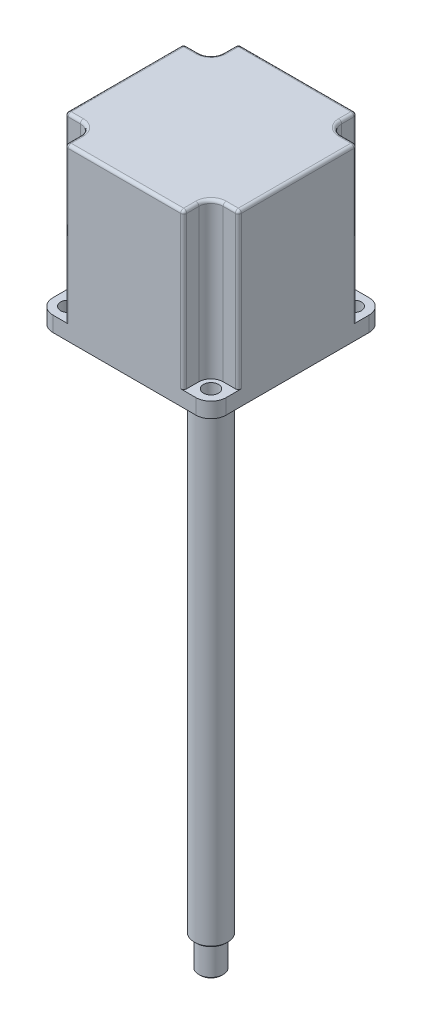
SolidWorks part; units mm, degrees
note: '?' marks a value the reader was unsure of.
material "1023 Carbon Steel Sheet (SS)"
ref_plane "Front" through (0, 0, 0) normal (0, 0, 1) x (1, 0, 0)
ref_plane "Top" through (0, 0, 0) normal (0, 1, 0) x (1, 0, 0)
ref_plane "Right" through (0, 0, 0) normal (1, 0, 0) x (0, 0, -1)
ref_axis "Axis1" through (-84.4107, 0, 0) along (1, 0, 0)?
ref_axis "Axis2" through (0, 64.3378, 0) along (0, -1, 0)?
ref_axis "Axis3" through (0, 0, -102.329) along (0, 0, 1)?
sketch "Sketch1" plane through (0, 0, 0) normal (0, 1, 0) x (1, 0, 0)
  line L1 (-28.5, -28.5) -> (28.5, -28.5)
  line L2 (-28.5, -28.5) -> (-28.5, 28.5)
  line L3 (-28.5, 28.5) -> (28.5, 28.5)
  line L4 (28.5, -28.5) -> (28.5, 28.5)
  line L5 (-28.5, -28.5) -> (28.5, 28.5) construction
  line L6 (-28.5, 28.5) -> (28.5, -28.5) construction
  point P0 (0, 0)
  dimension "D1" = 57
  dimension "D2" = 57
extrude "Extrude1" add sketch "Sketch1" along normal blind 76
hole_wizard "Ø5.0 (5) Diameter Hole1" positions "Sketch5" profile "Sketch4" hole size "Ø5.0" standard "ISO" end condition through all
sketch "Sketch5" plane through (0, 0, 0) normal (0, -1, 0) x (1, 0, 0)
  line L0 (-28.5, 28.5) -> (28.5, -28.5) construction
  line L3 (28.5, 28.5) -> (-28.5, -28.5) construction
  point P0 (-23.5, 23.5)
  point P1 (23.5, 23.5)
  point P3 (23.5, -23.5)
  point P5 (-23.5, -23.5)
  dimension "D1" = 47
  dimension "D2" = 47
sketch "Sketch4" plane through (-23.5, 0, 23.5) normal (1, 0, 0) x (0, 0, -1)
  line L0 (0, 0) -> (0, 76)
  line L1 (0, 76) -> (2.5, 76)
  line L2 (2.5, 76) -> (2.5, 0)
  line L5 (2.5, 0) -> (0, 0)
  line L11 (0, -6.35) -> (0, 107.95) construction
  dimension "Thru Hole Dia." = 5
  dimension "Thru Hole Depth" = 76
sketch "Sketch6" plane through (0, 76, 0) normal (0, 1, 0) x (1, 0, 0)
  line L0 (-19.5, 23.5) -> (-19.5, 32.5117)
  line L1 (-19.5, 32.5117) -> (-33.9089, 32.5117)
  line L2 (-33.9089, 32.5117) -> (-33.9089, 19.5)
  line L3 (-33.9089, 19.5) -> (-23.5, 19.5)
  line L4 (19.5, 23.5) -> (19.5, 36.4716)
  line L5 (19.5, 36.4716) -> (41.1684, 36.4716)
  line L6 (41.1684, 36.4716) -> (41.1684, 19.5)
  line L7 (41.1684, 19.5) -> (23.5, 19.5)
  line L8 (23.5, -19.5) -> (44.2522, -19.5)
  line L9 (44.2522, -19.5) -> (44.2522, -40.0504)
  line L10 (44.2522, -40.0504) -> (19.5, -40.0504)
  line L11 (19.5, -40.0504) -> (19.5, -23.5)
  line L12 (-23.5, -19.5) -> (-37.6708, -19.5)
  line L13 (-37.6708, -19.5) -> (-37.6708, -37.8282)
  line L14 (-37.6708, -37.8282) -> (-19.5, -37.8282)
  line L15 (-19.5, -37.8282) -> (-19.5, -23.5)
  circle A0 centre (-23.5, 23.5) radius 4
  circle A1 centre (23.5, 23.5) radius 4
  circle A2 centre (23.5, -23.5) radius 4
  circle A3 centre (-23.5, -23.5) radius 4
  circle M1 centre (-23.5, -23.5) radius 2.5
  circle M2 centre (23.5, -23.5) radius 2.5
  circle M3 centre (23.5, 23.5) radius 2.5
  circle M4 centre (-23.5, 23.5) radius 2.5
  line M5 (28.5, -28.5) -> (28.5, 28.5)
  line M6 (28.5, 28.5) -> (-28.5, 28.5)
  line M7 (-28.5, 28.5) -> (-28.5, -28.5)
  line M8 (-28.5, -28.5) -> (28.5, -28.5)
  dimension "D1" = 8
  dimension "D2" = 8
  dimension "D3" = 8
  dimension "D4" = 8
extrude "Extrude4" cut sketch "Sketch6" against normal blind 71 contours L2 L3 L0 L1 M7 M6 | A0 L0 L3 M6 M7 | A0 M4 | L7 L6 L5 L4 M6 M5 | A1 L7 L4 M5 M6 | A1 M3 | A2 M2 | A2 L11 L8 M8 M5 | L11 L10 L9 L8 M5 M8 | L14 L15 L12 L13 M8 M7 | A3 L12 L15 M7 M8 | A3 M1
fillet "Fillet1" radius 5 4 edges at (-28.5, 2.5, 28.5) (28.5, 2.5, 28.5) (28.5, 2.5, -28.5) (-28.5, 2.5, -28.5)
sketch "Sketch7" plane through (0, 76, 0) normal (0, 1, 0) x (1, 0, 0)
  circle A0 centre (0, 0) radius 3
  dimension "D1" = 6
extrude "Extrude5" add sketch "Sketch7" against normal blind 101 separate body
sketch "Sketch8" plane through (0, 0, 0) normal (0, -1, 0) x (1, 0, 0)
  circle A0 centre (0, 0) radius 15
  dimension "D1" = 30
extrude "Extrude6" add sketch "Sketch8" along normal blind 3
fillet "Fillet2" radius 1 24 edges at (-26, 76, 19.5) (-20.6716, 76, 20.6716) (-19.5, 76, 26) (0, 76, 28.5) (19.5, 76, 26) (20.6716, 76, 20.6716) (26, 76, 19.5) (28.5, 76, 0) (19.5, 76, -26) (26, 76, -19.5) (20.6716, 76, -20.6716) (-26, 76, -19.5) (-19.5, 76, -26) (-20.6716, 76, -20.6716) (0, 76, -28.5) (-28.5, 76, 0) (-19.5, 40.5, 28.5) (-28.5, 40.5, 19.5) (-28.5, 40.5, -19.5) (-19.5, 40.5, -28.5) (19.5, 40.5, -28.5) (28.5, 40.5, -19.5) (28.5, 40.5, 19.5) (19.5, 40.5, 28.5)
sketch "Sketch9" plane through (0, 0, 0) normal (0, -1, 0) x (1, 0, 0)
  circle A0 centre (0, 0) radius 5.5
  dimension "D1" = 11
extrude "Boss-Extrude1" add sketch "Sketch9" along normal blind 174
chamfer "Chamfer1" distance 0.5 angle 45 1 edges at (0, -174, -5.5)
sketch "Sketch10" plane through (0, -174, 0) normal (0, -1, 0) x (1, 0, 0)
  circle A0 centre (0, 0) radius 4
  dimension "D1" = 8
extrude "Boss-Extrude2" add sketch "Sketch10" along normal blind 10
chamfer "Chamfer2" distance 0.5 angle 45 1 edges at (0, -184, -4)
sketch "Sketch11" plane through (0, 0, 28.5) normal (0, 0, 1) x (1, 0, 0)
  line L0 (-23.5, 0) -> (23.5, 0) construction
  line L1 (-68.3145, 56) -> (68.6511, 56)
  line L2 (-68.3145, 56) -> (-68.3145, 114.8924)
  line L3 (-68.3145, 114.8924) -> (68.6511, 114.8924)
  line L4 (68.6511, 56) -> (68.6511, 114.8924)
  dimension "D1" = 56
extrude "Cut-Extrude1" cut sketch "Sketch11" against normal up to next
fillet "Fillet3" radius 1 24 edges at (19.2071, 56, 28.2071) (0, 56, 28.5) (-19.2071, 56, 28.2071) (-19.5, 56, 25.5) (-20.6716, 56, 20.6716) (-25.5, 56, 19.5) (-28.2071, 56, 19.2071) (-28.5, 56, 0) (-28.2071, 56, -19.2071) (-25.5, 56, -19.5) (-20.6716, 56, -20.6716) (-19.5, 56, -25.5) (-19.2071, 56, -28.2071) (0, 56, -28.5) (19.2071, 56, -28.2071) (19.5, 56, -25.5) (20.6716, 56, -20.6716) (25.5, 56, -19.5) (28.2071, 56, -19.2071) (28.5, 56, 0) (28.2071, 56, 19.2071) (25.5, 56, 19.5) (20.6716, 56, 20.6716) (19.5, 56, 25.5)
